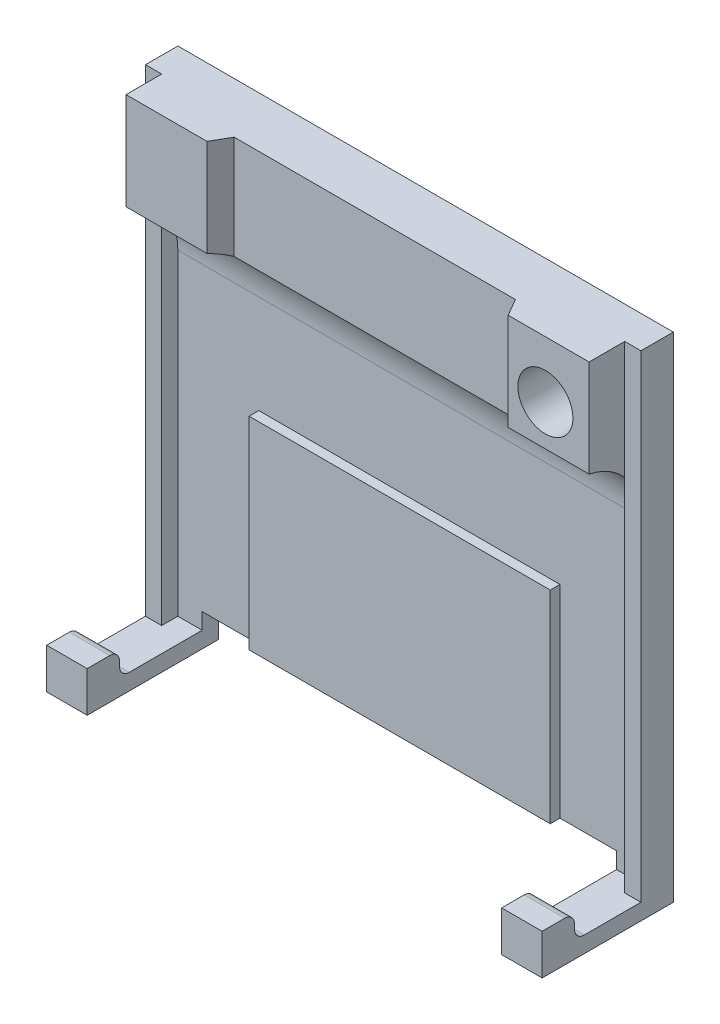
SolidWorks part; units mm, degrees
ref_plane "Plan de face" through (0, 0, 0) normal (0, 0, 1) x (1, 0, 0)
ref_plane "Plan de dessus" through (0, 0, 0) normal (0, 1, 0) x (1, 0, 0)
ref_plane "Plan de droite" through (0, 0, 0) normal (1, 0, 0) x (0, 0, -1)
sketch "Esquisse1" plane through (0, 0, 0) normal (0, 0, 1) x (1, 0, 0)
  line L5 (-14.3, 8.25) -> (14.3, 8.25)
  line L6 (-14.3, 8.25) -> (-14.3, -8.25)
  line L7 (-14.3, -8.25) -> (14.3, -8.25)
  line L8 (14.3, 8.25) -> (14.3, -8.25)
  line L9 (-14.3, 8.25) -> (14.3, -8.25) construction
  line L10 (-14.3, -8.25) -> (14.3, 8.25) construction
  point P4 (0, 0)
  dimension "D1" = 28.6
  dimension "D2" = 16.5
extrude "Boss.-Extru.1" add sketch "Esquisse1" along normal blind 1
sketch "Esquisse2" plane through (0, 0, 1) normal (0, 0, 1) x (1, 0, 0)
  line L0 (14.3, 8.25) -> (-14.3, 8.25) construction
  line L1 (-9.3, 4.25) -> (9.3, 4.25)
  line L2 (-9.3, 4.25) -> (-9.3, -8.25)
  line L3 (-9.3, -8.25) -> (9.3, -8.25)
  line L4 (9.3, 4.25) -> (9.3, -8.25)
  line L5 (-9.3, 4.25) -> (9.3, -8.25) construction
  line L6 (-9.3, -8.25) -> (9.3, 4.25) construction
  line L7 (0, -2) -> (0, 0) construction
  line L9 (-14.3, -8.25) -> (14.3, -8.25) construction
  line L10 (-14.3, 8.25) -> (-14.3, -8.25) construction
  point P0 (0, -2)
  dimension "D1" = 5
  dimension "D2" = 4
extrude "Boss.-Extru.2" add sketch "Esquisse2" along normal blind 0.6
sketch "Esquisse3" plane through (0, 0, 0) normal (0, 0, -1) x (-1, 0, 0)
  line L0 (14.3, 8.25) -> (14.3, -8.25) construction
  line L1 (-14.3, 8.25) -> (14.3, 8.25)
  line L2 (-14.3, 8.25) -> (-14.3, 20.25)
  line L3 (-14.3, 20.25) -> (14.3, 20.25)
  line L4 (14.3, 8.25) -> (14.3, 20.25)
  dimension "D1" = 12
extrude "Boss.-Extru.3" add sketch "Esquisse3" against normal blind 1
sketch "Esquisse4" plane through (0, 0, 1) normal (0, 0, 1) x (1, 0, 0)
  line L0 (14.3, -8.25) -> (14.3, 20.25) construction
  line L1 (-14.3, 20.25) -> (14.3, 20.25)
  line L2 (-14.3, 20.25) -> (-14.3, 14.25)
  line L3 (-14.3, 14.25) -> (14.3, 14.25)
  line L4 (14.3, 20.25) -> (14.3, 14.25)
  dimension "D1" = 6
extrude "Boss.-Extru.4" add sketch "Esquisse4" along normal blind 3.2
sketch "Esquisse5" plane through (0, 0, 0) normal (0, 0, -1) x (-1, 0, 0)
  line L0 (-14.3, 9.25) -> (14.3, 9.25) construction
  line L1 (-14.3, -8.25) -> (-14.3, 20.25) construction
  line L2 (14.3, 20.25) -> (14.3, -8.25) construction
  line L3 (14.3, 20.25) -> (-14.3, 20.25) construction
  circle A0 centre (-11.6, 16.75) radius 1.7
  dimension "D1" = 3.4
  dimension "D2" = 11
  dimension "D3" = 7.5
  dimension "D4" = 2.7
extrude "Enlèv. mat.-Extru.1" cut sketch "Esquisse5" against normal through all
fillet "Congé1" radius 4 1 edges at (0, 14.25, 1)
sketch "Esquisse6" plane through (0, -8.25, 0) normal (0, -1, 0) x (1, 0, 0)
  line L0 (-14.3, 0) -> (14.3, 0) construction
  line L1 (-14.3, 1) -> (-12.8, 1)
  line L2 (-14.3, 1) -> (-14.3, 0)
  line L3 (-14.3, 0) -> (-12.8, 0)
  line L4 (-12.8, 1) -> (-12.8, 0)
  line L6 (14.3, 1) -> (12.8, 1)
  line L7 (14.3, 1) -> (14.3, 0)
  line L8 (14.3, 0) -> (12.8, 0)
  line L9 (12.8, 1) -> (12.8, 0)
  dimension "D1" = 1.5
  dimension "D2" = 1.5
extrude "Boss.-Extru.5" add sketch "Esquisse6" along normal blind 2
sketch "Esquisse7" plane through (0, 0, 1) normal (0, 0, 1) x (1, 0, 0)
  line L0 (-12.8, -10.25) -> (-14.3, -10.25) construction
  line L1 (-12.8, -9.25) -> (-15.3, -9.25)
  line L2 (-12.8, -9.25) -> (-12.8, -10.25)
  line L3 (-12.8, -10.25) -> (-15.3, -10.25)
  line L4 (-15.3, -9.25) -> (-15.3, -10.25)
  line L5 (12.8, -9.25) -> (15.3, -9.25)
  line L6 (12.8, -9.25) -> (12.8, -10.25)
  line L7 (12.8, -10.25) -> (15.3, -10.25)
  line L8 (15.3, -9.25) -> (15.3, -10.25)
  line L9 (-14.3, 10.3308) -> (-14.3, -10.25) construction
  line L10 (14.3, -10.25) -> (14.3, 10.3308) construction
  dimension "D1" = 1
  dimension "D2" = 1
  dimension "D3" = 1
  dimension "D4" = 1
extrude "Boss.-Extru.6" add sketch "Esquisse7" along normal blind 7.1
sketch "Esquisse8" plane through (0, -9.25, 0) normal (0, 1, 0) x (1, 0, 0)
  line L0 (-12.8, -8.1) -> (-12.8, -1) construction
  line L1 (-15.3, -8.1) -> (-12.8, -8.1)
  line L2 (-15.3, -8.1) -> (-15.3, -6.1)
  line L3 (-15.3, -6.1) -> (-12.8, -6.1)
  line L4 (-12.8, -8.1) -> (-12.8, -6.1)
  line L5 (15.3, -8.1) -> (15.3, -1) construction
  line L6 (12.8, -8.1) -> (15.3, -8.1)
  line L7 (12.8, -8.1) -> (12.8, -6.1)
  line L8 (12.8, -6.1) -> (15.3, -6.1)
  line L9 (15.3, -8.1) -> (15.3, -6.1)
  dimension "D1" = 2
extrude "Boss.-Extru.7" add sketch "Esquisse8" along normal blind 1.5
fillet "Congé2" radius 0.6 4 edges at (14.05, -7.75, 6.1) (-14.05, -7.75, 6.1) (-14.05, -9.25, 6.1) (14.05, -9.25, 6.1)
sketch "Esquisse9" plane through (0, 0, 0) normal (0, 0, -1) x (-1, 0, 0)
  line L0 (14.3, 20.25) -> (-14.3, 20.25) construction
  line L1 (-14.3, -10.25) -> (-15.3, -10.25)
  line L2 (-14.3, -10.25) -> (-14.3, 20.25)
  line L3 (-14.3, 20.25) -> (-15.3, 20.25)
  line L4 (-15.3, -10.25) -> (-15.3, 20.25)
  line L5 (14.3, -10.25) -> (15.3, -10.25)
  line L6 (14.3, -10.25) -> (14.3, 20.25)
  line L7 (14.3, 20.25) -> (15.3, 20.25)
  line L8 (15.3, -10.25) -> (15.3, 20.25)
  line L9 (14.3, 20.25) -> (14.3, -10.25) construction
  dimension "D1" = 1
  dimension "D2" = 1
extrude "Boss.-Extru.8" add sketch "Esquisse9" against normal blind 2
chamfer "Chanfrein2" distance 1 angle 45 1 edges at (9.9, 16.75, 0)
sketch "Esquisse10" plane through (0, 20.25, 0) normal (0, 1, 0) x (1, 0, 0)
  line L0 (9.3, -4.2) -> (8.6859, -3.1364)
  line L1 (14.3, -4.2) -> (-14.3, -4.2) construction
  line L2 (8.6859, -3.1364) -> (-8.6859, -3.1364)
  line L3 (-8.6859, -3.1364) -> (-9.3, -4.2)
  line L4 (-9.3, -4.2) -> (9.3, -4.2)
  line L5 (14.3, -4.2) -> (14.3, -2) construction
  dimension "D1" = 5
  dimension "D2" = 5
  dimension "D3" = 120
  dimension "D4" = 120
extrude "Enlèv. mat.-Extru.2" cut sketch "Esquisse10" against normal blind 10
